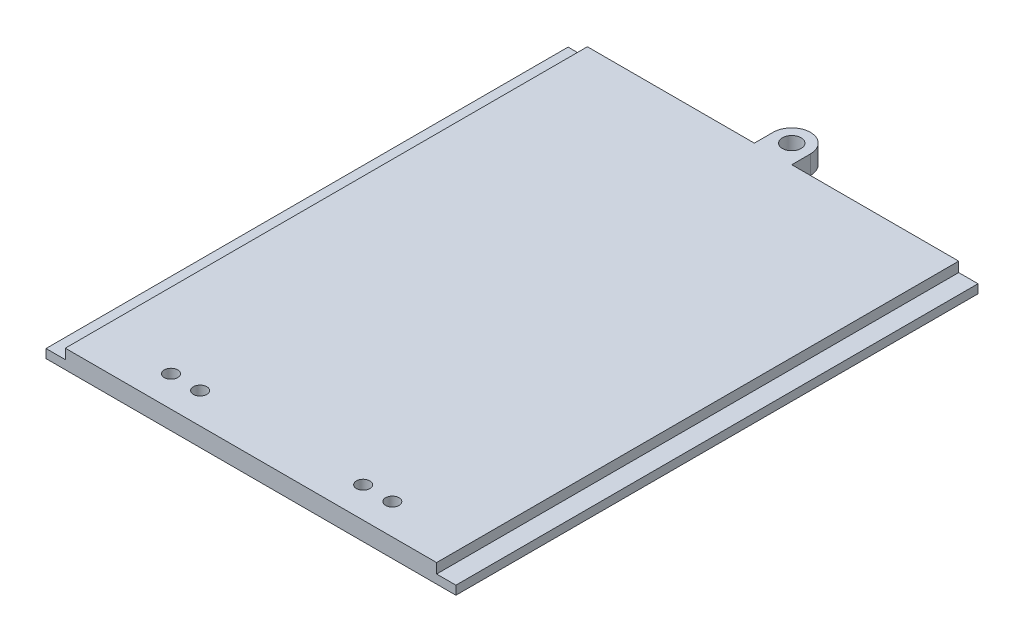
SolidWorks part; units mm, degrees
ref_plane "Front Plane" through (0, 0, 0) normal (0, 0, 1) x (1, 0, 0)
ref_plane "Top Plane" through (0, 0, 0) normal (0, 1, 0) x (1, 0, 0)
ref_plane "Right Plane" through (0, 0, 0) normal (1, 0, 0) x (0, 0, -1)
sketch "Sketch1" plane through (0, 0, 0) normal (0, 1, 0) x (1, 0, 0)
  line L1 (0, 0) -> (139.192, 0)
  line L2 (0, 0) -> (0, 177.292)
  line L3 (0, 177.292) -> (139.192, 177.292)
  line L4 (139.192, 0) -> (139.192, 177.292)
  dimension "D1" = 139.192
  dimension "D2" = 177.292
extrude "Boss-Extrude1" add sketch "Sketch1" along normal blind 6.35
sketch "Sketch2" plane through (0, 6.35, 0) normal (0, 1, 0) x (1, 0, 0)
  line L0 (69.596, 177.292) -> (69.596, 0) construction
  line L1 (139.192, 177.292) -> (0, 177.292) construction
  line L2 (0, 0) -> (139.192, 0) construction
  line L3 (132.642, 177.292) -> (132.642, 0)
  line L4 (0, 177.292) -> (6.55, 177.292)
  line L5 (0, 177.292) -> (0, 0)
  line L6 (0, 0) -> (6.55, 0)
  line L7 (6.55, 177.292) -> (6.55, 0)
  line L8 (139.192, 0) -> (132.642, 0)
  line L9 (139.192, 177.292) -> (139.192, 0)
  line L10 (139.192, 177.292) -> (132.642, 177.292)
  dimension "D1" = 6.55
extrude "Cut-Extrude1" cut sketch "Sketch2" against normal blind 3.375
sketch "Sketch3" plane through (0, 6.35, 0) normal (0, 1, 0) x (1, 0, 0)
  line L0 (132.642, 177.292) -> (6.55, 177.292) construction
  line L1 (63.246, 177.292) -> (75.946, 177.292)
  line L2 (63.246, 177.292) -> (63.246, 189.992)
  line L3 (63.246, 189.992) -> (75.946, 189.992)
  line L4 (75.946, 177.292) -> (75.946, 189.992)
  line L5 (139.192, 177.292) -> (0, 177.292) construction
  line L7 (139.192, 0) -> (139.192, 177.292) construction
  line L8 (0, 177.292) -> (0, 0) construction
  point P6 (69.596, 177.292)
  point P9 (69.596, 177.292)
  dimension "D1" = 12.7
  dimension "D2" = 12.7
  dimension "D3" = 63.246
  dimension "D4" = 63.246
extrude "Boss-Extrude2" add sketch "Sketch3" against normal blind 6.35
fillet "Fillet1" radius 6.35 2 edges at (63.246, 3.175, -189.992) (75.946, 3.175, -189.992)
sketch "Sketch4" plane through (0, 6.35, 0) normal (0, 1, 0) x (1, 0, 0)
  circle A0 centre (69.596, 183.642) radius 3.175
  dimension "D1" = 6.35
extrude "Cut-Extrude2" cut sketch "Sketch4" against normal through all
sketch "Sketch5" plane through (0, 0, 0) normal (0, -1, 0) x (1, 0, 0)
  line L0 (107.188, -8.128) -> (107.188, 0) construction
  line L1 (0, 0) -> (139.192, 0) construction
  line L2 (109.474, -10.414) -> (139.192, -10.414) construction
  line L3 (139.192, 0) -> (139.192, -177.292) construction
  line L4 (104.902, -10.414) -> (99.568, -10.414) construction
  line L5 (39.624, -10.414) -> (34.29, -10.414) construction
  line L7 (94.996, -10.414) -> (44.196, -10.414) construction
  line L8 (29.718, -10.414) -> (0, -10.414) construction
  line L9 (0, -177.292) -> (0, 0) construction
  circle A0 centre (107.188, -10.414) radius 2.286
  circle A1 centre (97.282, -10.414) radius 2.286
  circle A2 centre (41.91, -10.414) radius 2.286
  circle A3 centre (32.004, -10.414) radius 2.286
  dimension "D2" = 4.572
  dimension "D3" = 4.572
  dimension "D4" = 4.572
  dimension "D5" = 4.572
  dimension "D1" = 8.128
  dimension "D6" = 5.334
  dimension "D7" = 5.334
  dimension "D8" = 50.8
extrude "Cut-Extrude3" cut sketch "Sketch5" against normal blind 12.7
